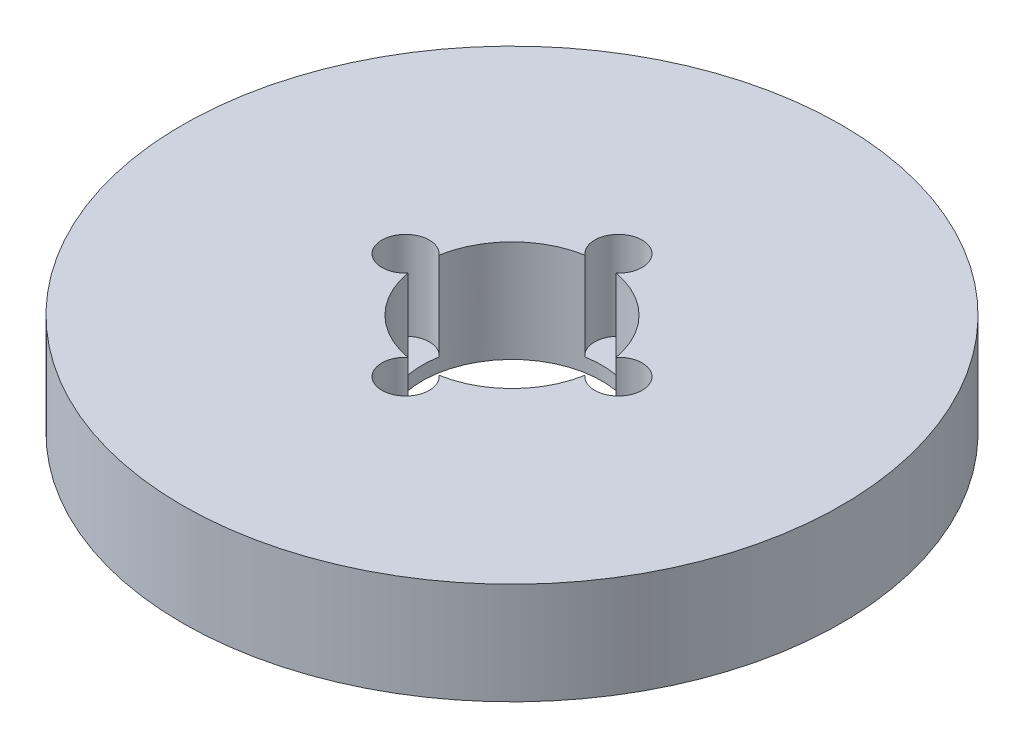
SolidWorks part; units mm, degrees
ref_plane "Front Plane" through (0, 0, 0) normal (0, 0, 1) x (1, 0, 0)
ref_plane "Top Plane" through (0, 0, 0) normal (0, 1, 0) x (1, 0, 0)
ref_plane "Right Plane" through (0, 0, 0) normal (1, 0, 0) x (0, 0, -1)
sketch "Sketch1" plane through (0, 0, 0) normal (0, 1, 0) x (1, 0, 0)
  circle A0 centre (0, 0) radius 55
  dimension "FLANGE_OD" = 110
extrude "Boss-Extrude1" add sketch "Sketch1" along normal blind 17
sketch "Sketch2" plane through (0, 0, 0) normal (0, 1, 0) x (1, 0, 0)
  circle A0 centre (0, 0) radius 15
  dimension "BORE_D" = 30
extrude "Cut-Extrude1" cut sketch "Sketch2" along normal through all
sketch "Sketch3" plane through (0, 17, 0) normal (0, 1, 0) x (1, 0, 0)
  circle A0 centre (0, 0) radius 17.7589 construction
  circle A1 centre (-17.7589, 0) radius 3.9649
  dimension "BOLT_D" = 7.9298
  dimension "BOLT_PCD" = 35.5178
extrude "Cut-Extrude2" cut sketch "Sketch3" against normal blind 14.7206
pattern_circular "CirPattern1" count 4 over 360 about axis through (0, 0, 0) along (0, 1, 0) of "Cut-Extrude2"
